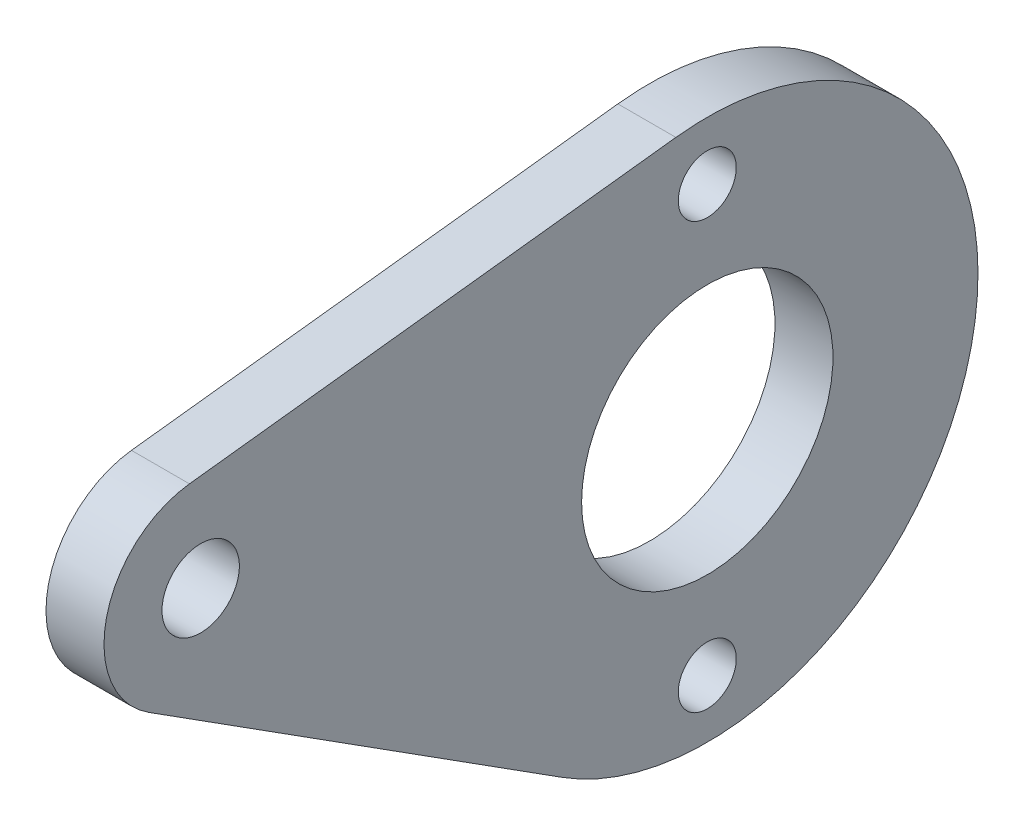
SolidWorks part; units mm, degrees
ref_plane "Plan de face" through (0, 0, 0) normal (0, 0, 1) x (1, 0, 0)
ref_plane "Plan de dessus" through (0, 0, 0) normal (0, 1, 0) x (1, 0, 0)
ref_plane "Plan de droite" through (0, 0, 0) normal (1, 0, 0) x (0, 0, -1)
sketch "Esquisse1" plane through (0, 0, 0) normal (-1, 0, 0) x (0, 0, 1)
  line L0 (28.8837, 1.7813) -> (7.5143, -11.8125)
  line L1 (1.6247, 13.9054) -> (26.7803, 10.9662)
  arc A0 (7.5143, -11.8125) -> (1.6247, 13.9054) centre (0, 0) cw
  arc A1 (26.7803, 10.9662) -> (28.8837, 1.7813) centre (26.2, 6) cw
  circle A2 centre (0, 0) radius 6.5 construction
  circle A3 centre (0, 0) radius 6.5
  circle A5 centre (0, 11) radius 1.5
  circle A6 centre (0, -11) radius 1.5
  circle A7 centre (0, 0) radius 14 construction
  circle A8 centre (26.2, 6) radius 2
  dimension "D1" = 3
  dimension "D2" = 4
  dimension "D3" = 5
extrude "Boss.-Extru.1" add sketch "Esquisse1" against normal blind 3
